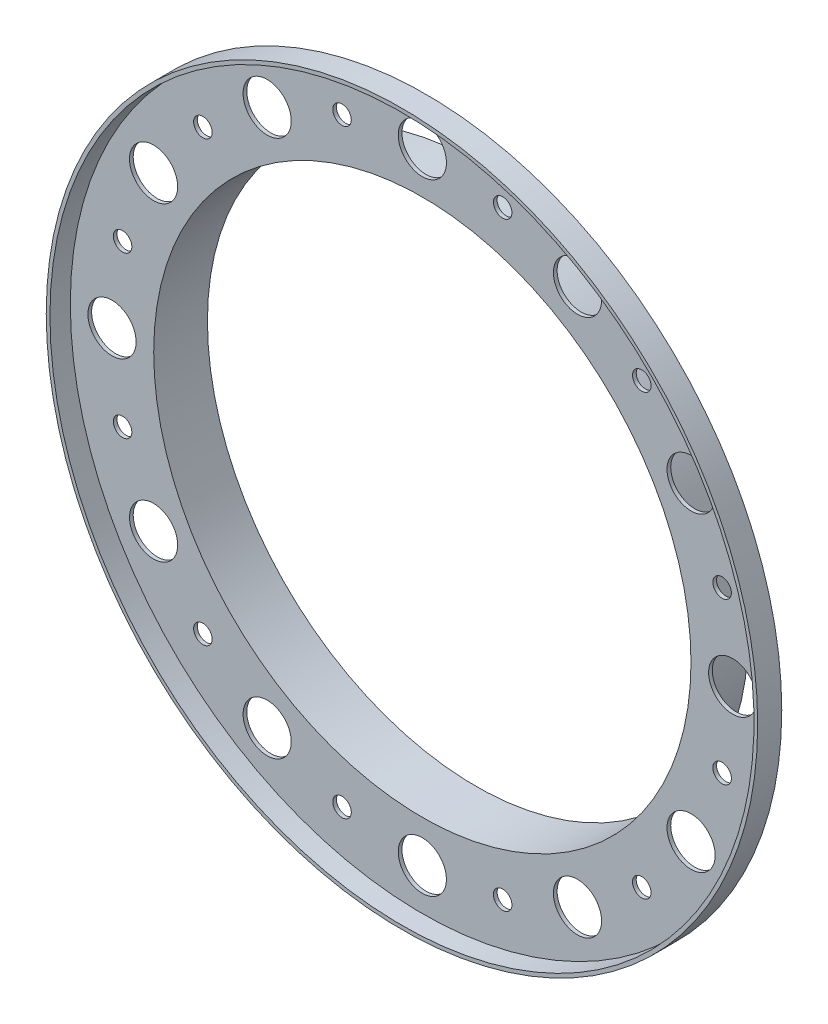
SolidWorks part; units mm, degrees
note: '?' marks a value the reader was unsure of.
material "AISI Type 316L stainless steel"
ref_plane "Front Plane" through (0, 0, 0) normal (0, 0, 1) x (1, 0, 0)
ref_plane "Top Plane" through (0, 0, 0) normal (0, 1, 0) x (1, 0, 0)
ref_plane "Right Plane" through (0, 0, 0) normal (1, 0, 0) x (0, 0, -1)
sketch "Sketch1" plane through (0, 0, 0) normal (1, 0, 0) x (0, 0, -1)
  line L0 (0, 0) -> (-44.553, 0) construction
  line L1 (0, 29) -> (-5.8, 29)
  line L2 (-5.8, 29) -> (-5.8, 38)
  line L3 (-5.8, 38) -> (-8, 38)
  dimension "D1" = 58
  dimension "D2" = 76
  dimension "D3" = 2.2
  dimension "D4" = 8
revolve "Revolve-Thin1" add sketch "Sketch1" angle 360 about L0
sketch "Sketch2" plane through (0, 0, 5.8) normal (0, 0, 1) x (1, 0, 0)
  line L0 (-8.6704, 32.3585) -> (0, 0) construction
  line L1 (0, 0) -> (0, 33.5) construction
  circle A0 centre (0, 33.5) radius 2.6
  circle A1 centre (-8.6704, 32.3585) radius 1
  circle A2 centre (0, 0) radius 33.5 construction
  dimension "D1" = 67
  dimension "D3" = 2
  dimension "D4" = 5.2
  dimension "D2" = 15
extrude "Cut-Extrude1" cut sketch "Sketch2" against normal through all
ref_axis "Axis1" through (0, 0, 8.4) along (0, 0, -1)?
pattern_circular "CirPattern1" count 12 over 360 about axis through (0, 0, 0) along (0, 0, 1) of "Cut-Extrude1"
